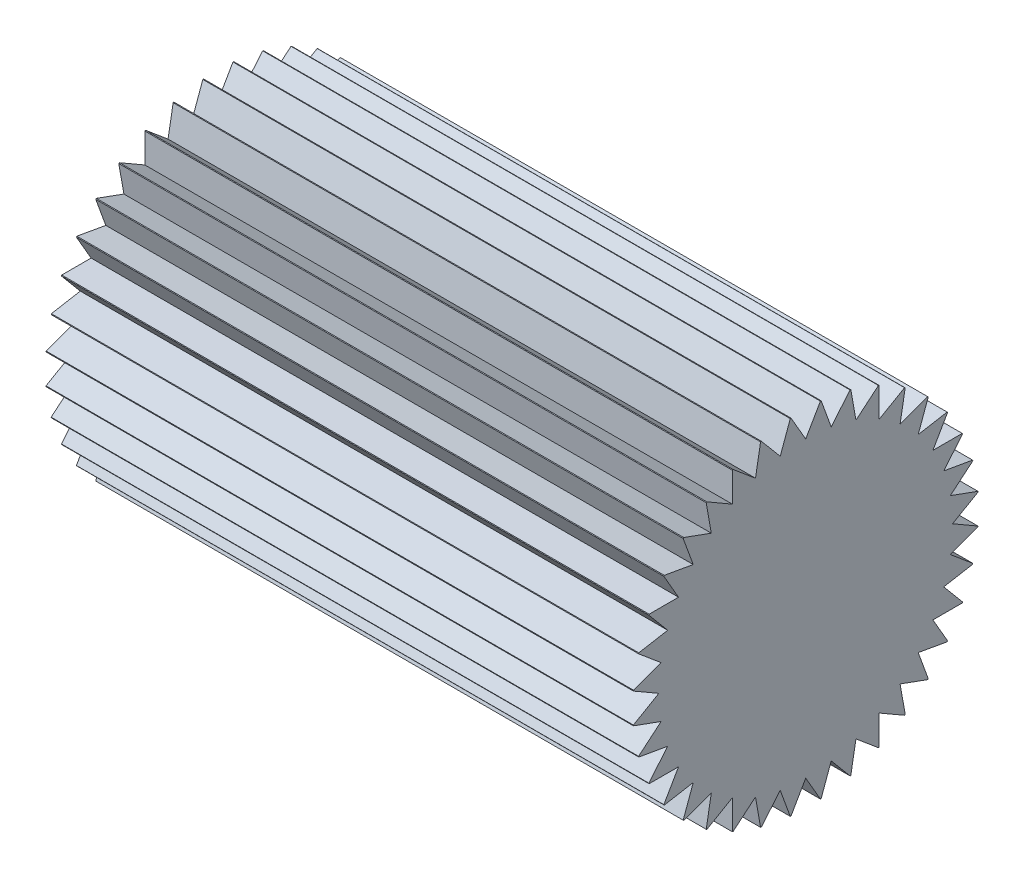
SolidWorks part; units mm, degrees
ref_plane "Front Plane" through (0, 0, 0) normal (0, 0, 1) x (1, 0, 0)
ref_plane "Top Plane" through (0, 0, 0) normal (0, 1, 0) x (1, 0, 0)
ref_plane "Right Plane" through (0, 0, 0) normal (1, 0, 0) x (0, 0, -1)
sketch "Sketch1" plane through (0, 0, 0) normal (1, 0, 0) x (0, 0, -1)
  line L101 (0, 0) -> (0, 17.584) construction
  line L102 (-1, 11.7321) -> (0, 10)
  line L105 (1.0524, 11.7275) -> (1.7365, 9.8481)
  line L106 (3.0221, 11.3802) -> (1.7365, 9.8481)
  line L111 (5, 10.6603) -> (5, 8.6603)
  line L112 (6.7321, 9.6603) -> (5, 8.6603)
  line L113 (6.7752, 9.6301) -> (6.4279, 7.6604)
  line L114 (8.3073, 8.3445) -> (6.4279, 7.6604)
  line L115 (8.3445, 8.3073) -> (7.6604, 6.4279)
  line L116 (9.6301, 6.7752) -> (7.6604, 6.4279)
  line L117 (9.6603, 6.7321) -> (8.6603, 5)
  line L118 (10.6603, 5) -> (8.6603, 5)
  line L119 (10.6825, 4.9523) -> (9.3969, 3.4202)
  line L120 (11.3665, 3.0729) -> (9.3969, 3.4202)
  line L121 (11.3802, 3.0221) -> (9.8481, 1.7365)
  line L122 (11.7275, 1.0524) -> (9.8481, 1.7365)
  line L123 (11.7321, 1) -> (10, 0)
  line L124 (11.7321, -1) -> (10, 0)
  line L125 (11.7275, -1.0524) -> (9.8481, -1.7365)
  line L126 (11.3802, -3.0221) -> (9.8481, -1.7365)
  line L127 (1, 11.7321) -> (0, 10)
  line L128 (11.3665, -3.0729) -> (9.3969, -3.4202)
  line L129 (10.6825, -4.9523) -> (9.3969, -3.4202)
  line L130 (10.6603, -5) -> (8.6603, -5)
  line L131 (9.6603, -6.7321) -> (8.6603, -5)
  line L132 (9.6301, -6.7752) -> (7.6604, -6.4279)
  line L133 (8.3445, -8.3073) -> (7.6604, -6.4279)
  line L134 (8.3073, -8.3445) -> (6.4279, -7.6604)
  line L135 (6.7752, -9.6301) -> (6.4279, -7.6604)
  line L136 (6.7321, -9.6603) -> (5, -8.6603)
  line L137 (5, -10.6603) -> (5, -8.6603)
  line L138 (4.9523, -10.6825) -> (3.4202, -9.3969)
  line L139 (3.0729, -11.3665) -> (3.4202, -9.3969)
  line L140 (3.0221, -11.3802) -> (1.7365, -9.8481)
  line L141 (1.0524, -11.7275) -> (1.7365, -9.8481)
  line L142 (1, -11.7321) -> (0, -10)
  line L143 (-1, -11.7321) -> (0, -10)
  line L144 (-1.0524, -11.7275) -> (-1.7365, -9.8481)
  line L145 (-3.0221, -11.3802) -> (-1.7365, -9.8481)
  line L146 (-3.0729, -11.3665) -> (-3.4202, -9.3969)
  line L147 (-4.9523, -10.6825) -> (-3.4202, -9.3969)
  line L148 (-5, -10.6603) -> (-5, -8.6603)
  line L149 (-6.7321, -9.6603) -> (-5, -8.6603)
  line L150 (-6.7752, -9.6301) -> (-6.4279, -7.6604)
  line L151 (-8.3073, -8.3445) -> (-6.4279, -7.6604)
  line L152 (-8.3445, -8.3073) -> (-7.6604, -6.4279)
  line L153 (-9.6301, -6.7752) -> (-7.6604, -6.4279)
  line L154 (-9.6603, -6.7321) -> (-8.6603, -5)
  line L155 (-10.6603, -5) -> (-8.6603, -5)
  line L156 (-10.6825, -4.9523) -> (-9.3969, -3.4202)
  line L157 (-11.3665, -3.0729) -> (-9.3969, -3.4202)
  line L158 (-11.3802, -3.0221) -> (-9.8481, -1.7365)
  line L159 (-11.7275, -1.0524) -> (-9.8481, -1.7365)
  line L160 (-11.7321, -1) -> (-10, 0)
  line L161 (-11.7321, 1) -> (-10, 0)
  line L162 (-11.7275, 1.0524) -> (-9.8481, 1.7365)
  line L163 (-11.3802, 3.0221) -> (-9.8481, 1.7365)
  line L164 (-11.3665, 3.0729) -> (-9.3969, 3.4202)
  line L165 (-10.6825, 4.9523) -> (-9.3969, 3.4202)
  line L166 (-10.6603, 5) -> (-8.6603, 5)
  line L167 (-9.6603, 6.7321) -> (-8.6603, 5)
  line L168 (-9.6301, 6.7752) -> (-7.6604, 6.4279)
  line L169 (-8.3445, 8.3073) -> (-7.6604, 6.4279)
  line L170 (-8.3073, 8.3445) -> (-6.4279, 7.6604)
  line L171 (-6.7752, 9.6301) -> (-6.4279, 7.6604)
  line L172 (-6.7321, 9.6603) -> (-5, 8.6603)
  line L173 (-5, 10.6603) -> (-5, 8.6603)
  line L174 (-4.9523, 10.6825) -> (-3.4202, 9.3969)
  line L175 (-3.0729, 11.3665) -> (-3.4202, 9.3969)
  line L176 (-3.0221, 11.3802) -> (-1.7365, 9.8481)
  line L177 (-1.0524, 11.7275) -> (-1.7365, 9.8481)
  line L178 (3.0729, 11.3665) -> (3.4202, 9.3969)
  line L179 (4.9523, 10.6825) -> (3.4202, 9.3969)
  arc A53 (1.0524, 11.7275) -> (1, 11.7321) centre (0, 0) ccw
  arc A55 (5, 10.6603) -> (4.9523, 10.6825) centre (0, 0) ccw
  arc A56 (6.7752, 9.6301) -> (6.7321, 9.6603) centre (0, 0) ccw
  arc A57 (8.3445, 8.3073) -> (8.3073, 8.3445) centre (0, 0) ccw
  arc A58 (9.6603, 6.7321) -> (9.6301, 6.7752) centre (0, 0) ccw
  arc A59 (10.6825, 4.9523) -> (10.6603, 5) centre (0, 0) ccw
  arc A60 (11.3802, 3.0221) -> (11.3665, 3.0729) centre (0, 0) ccw
  arc A61 (11.7321, 1) -> (11.7275, 1.0524) centre (0, 0) ccw
  arc A62 (11.7275, -1.0524) -> (11.7321, -1) centre (0, 0) ccw
  arc A63 (11.3665, -3.0729) -> (11.3802, -3.0221) centre (0, 0) ccw
  arc A64 (10.6603, -5) -> (10.6825, -4.9523) centre (0, 0) ccw
  arc A65 (9.6301, -6.7752) -> (9.6603, -6.7321) centre (0, 0) ccw
  arc A66 (8.3073, -8.3445) -> (8.3445, -8.3073) centre (0, 0) ccw
  arc A67 (6.7321, -9.6603) -> (6.7752, -9.6301) centre (0, 0) ccw
  arc A68 (4.9523, -10.6825) -> (5, -10.6603) centre (0, 0) ccw
  arc A69 (3.0221, -11.3802) -> (3.0729, -11.3665) centre (0, 0) ccw
  arc A70 (1, -11.7321) -> (1.0524, -11.7275) centre (0, 0) ccw
  arc A71 (-1.0524, -11.7275) -> (-1, -11.7321) centre (0, 0) ccw
  arc A72 (-3.0729, -11.3665) -> (-3.0221, -11.3802) centre (0, 0) ccw
  arc A73 (-5, -10.6603) -> (-4.9523, -10.6825) centre (0, 0) ccw
  arc A74 (-6.7752, -9.6301) -> (-6.7321, -9.6603) centre (0, 0) ccw
  arc A75 (-8.3445, -8.3073) -> (-8.3073, -8.3445) centre (0, 0) ccw
  arc A76 (-9.6603, -6.7321) -> (-9.6301, -6.7752) centre (0, 0) ccw
  arc A77 (-10.6825, -4.9523) -> (-10.6603, -5) centre (0, 0) ccw
  arc A78 (-11.3802, -3.0221) -> (-11.3665, -3.0729) centre (0, 0) ccw
  arc A79 (-11.7321, -1) -> (-11.7275, -1.0524) centre (0, 0) ccw
  arc A80 (-11.7275, 1.0524) -> (-11.7321, 1) centre (0, 0) ccw
  arc A81 (-11.3665, 3.0729) -> (-11.3802, 3.0221) centre (0, 0) ccw
  arc A82 (-10.6603, 5) -> (-10.6825, 4.9523) centre (0, 0) ccw
  arc A83 (-9.6301, 6.7752) -> (-9.6603, 6.7321) centre (0, 0) ccw
  arc A84 (-8.3073, 8.3445) -> (-8.3445, 8.3073) centre (0, 0) ccw
  arc A85 (-6.7321, 9.6603) -> (-6.7752, 9.6301) centre (0, 0) ccw
  arc A86 (-4.9523, 10.6825) -> (-5, 10.6603) centre (0, 0) ccw
  arc A87 (-3.0221, 11.3802) -> (-3.0729, 11.3665) centre (0, 0) ccw
  arc A88 (-1, 11.7321) -> (-1.0524, 11.7275) centre (0, 0) ccw
  arc A89 (3.0729, 11.3665) -> (3.0221, 11.3802) centre (0, 0) ccw
  point P12 (0, 0)
  point P16 (0, 0)
  point P17 (0, 0)
  point P156 (0, 0)
  dimension "D1" = 30
  dimension "D2" = 2
  dimension "D3" = 10
  dimension "D4" = 3
extrude "Boss-Extrude1" add sketch "Sketch1" along normal blind 40
